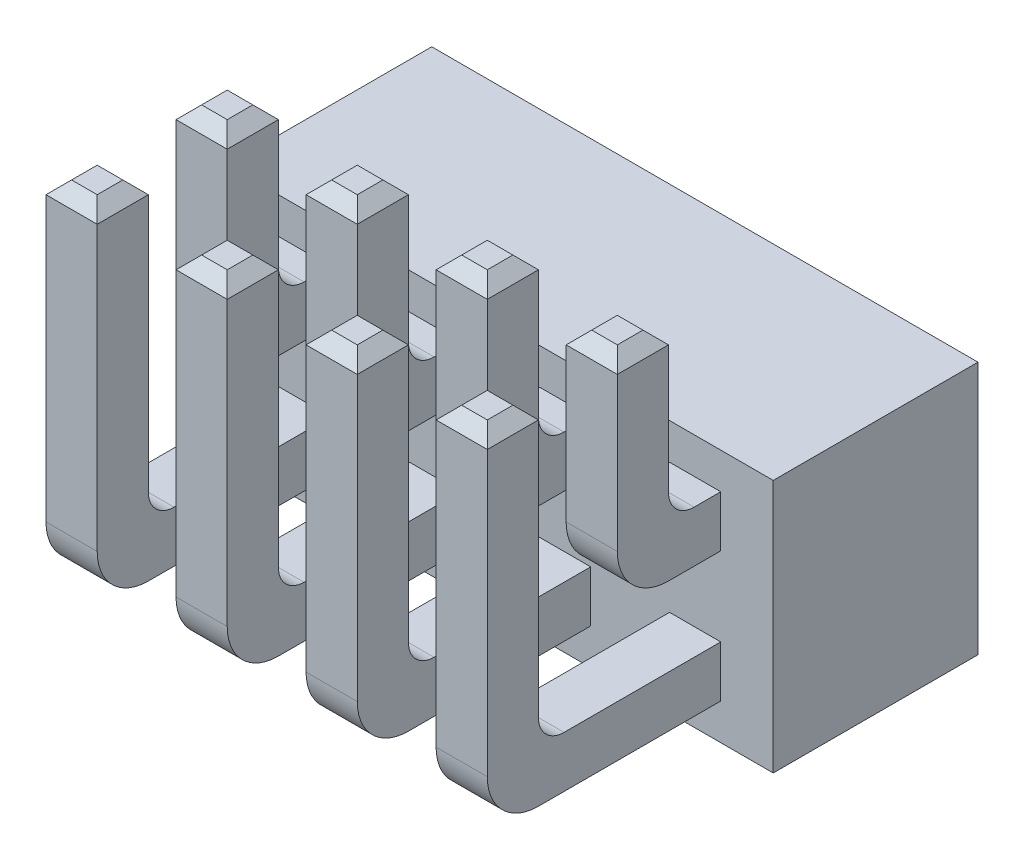
SolidWorks part; units mm, degrees
ref_plane "Front Plane" through (0, 0, 0) normal (0, 0, 1) x (1, 0, 0)
ref_plane "Top Plane" through (0, 0, 0) normal (0, 1, 0) x (1, 0, 0)
ref_plane "Right Plane" through (0, 0, 0) normal (1, 0, 0) x (0, 0, -1)
sketch "Sketch1" plane through (0, 0, 0) normal (0, 0, 1) x (1, 0, 0)
  line L1 (-5.335, 2.475) -> (5.335, 2.475)
  line L2 (-5.335, 2.475) -> (-5.335, -2.475)
  line L3 (-5.335, -2.475) -> (5.335, -2.475)
  line L4 (5.335, 2.475) -> (5.335, -2.475)
  line L5 (-5.335, 2.475) -> (5.335, -2.475) construction
  line L6 (-5.335, -2.475) -> (5.335, 2.475) construction
  point P0 (0, 0)
  point P10 (-8.3938, 4.4059)
  dimension "D1" = 10.67
  dimension "D2" = 4.95
extrude "Boss-Extrude1" add sketch "Sketch1" along normal blind 4
sketch "Sketch3" plane through (0, 0, 0) normal (0, 0, -1) x (-1, 0, 0)
  line L0 (-0.5788, 0.5788) -> (-1.9612, 0.5788)
  line L5 (-3.1188, 0.5788) -> (-4.5012, 0.5788)
  line L6 (-3.1188, 0.5788) -> (-3.1188, 1.9612)
  line L7 (-3.1188, 1.9612) -> (-4.5012, 1.9612)
  line L8 (-4.5012, 0.5788) -> (-4.5012, 1.9612)
  line L9 (-3.1188, 0.5788) -> (-4.5012, 1.9612) construction
  line L10 (-3.1188, 1.9612) -> (-4.5012, 0.5788) construction
  line L11 (-0.5788, 0.5788) -> (-0.5788, 1.9612)
  line L12 (-0.5788, 1.9612) -> (-1.9612, 1.9612)
  line L13 (-1.9612, 0.5788) -> (-1.9612, 1.9612)
  line L14 (-0.5788, 0.5788) -> (-1.9612, 1.9612) construction
  line L15 (-0.5788, 1.9612) -> (-1.9612, 0.5788) construction
  line L16 (1.9612, 0.5788) -> (0.5788, 0.5788)
  line L17 (1.9612, 0.5788) -> (1.9612, 1.9612)
  line L18 (1.9612, 1.9612) -> (0.5788, 1.9612)
  line L19 (0.5788, 0.5788) -> (0.5788, 1.9612)
  line L20 (1.9612, 0.5788) -> (0.5788, 1.9612) construction
  line L21 (1.9612, 1.9612) -> (0.5788, 0.5788) construction
  line L22 (4.5012, 0.5788) -> (3.1188, 0.5788)
  line L23 (4.5012, 0.5788) -> (4.5012, 1.9612)
  line L24 (4.5012, 1.9612) -> (3.1188, 1.9612)
  line L25 (3.1188, 0.5788) -> (3.1188, 1.9612)
  line L26 (4.5012, 0.5788) -> (3.1188, 1.9612) construction
  line L27 (4.5012, 1.9612) -> (3.1188, 0.5788) construction
  line L28 (-0.5788, -1.9612) -> (-1.9612, -1.9612)
  line L29 (-0.5788, -1.9612) -> (-0.5788, -0.5788)
  line L30 (-0.5788, -0.5788) -> (-1.9612, -0.5788)
  line L31 (-1.9612, -1.9612) -> (-1.9612, -0.5788)
  line L32 (-0.5788, -1.9612) -> (-1.9612, -0.5788) construction
  line L33 (-0.5788, -0.5788) -> (-1.9612, -1.9612) construction
  line L34 (1.9612, -1.9612) -> (0.5788, -1.9612)
  line L35 (1.9612, -1.9612) -> (1.9612, -0.5788)
  line L36 (1.9612, -0.5788) -> (0.5788, -0.5788)
  line L37 (0.5788, -1.9612) -> (0.5788, -0.5788)
  line L38 (1.9612, -1.9612) -> (0.5788, -0.5788) construction
  line L39 (1.9612, -0.5788) -> (0.5788, -1.9612) construction
  line L40 (4.5012, -1.9612) -> (3.1188, -1.9612)
  line L41 (4.5012, -1.9612) -> (4.5012, -0.5788)
  line L42 (4.5012, -0.5788) -> (3.1188, -0.5788)
  line L43 (3.1188, -1.9612) -> (3.1188, -0.5788)
  line L44 (4.5012, -1.9612) -> (3.1188, -0.5788) construction
  line L45 (4.5012, -0.5788) -> (3.1188, -1.9612) construction
  line L46 (-3.1188, -1.9612) -> (-4.5012, -1.9612)
  line L47 (-3.1188, -1.9612) -> (-3.1188, -0.5788)
  line L48 (-3.1188, -0.5788) -> (-4.5012, -0.5788)
  line L49 (-4.5012, -1.9612) -> (-4.5012, -0.5788)
  line L50 (-3.1188, -1.9612) -> (-4.5012, -0.5788) construction
  line L51 (-3.1188, -0.5788) -> (-4.5012, -1.9612) construction
  line L52 (-1.27, -1.27) -> (1.27, -1.27) construction
  line L53 (-3.81, 1.27) -> (-3.81, -1.27) construction
  point P0 (-3.81, 1.27)
  point P6 (-1.27, 1.27)
  point P12 (1.27, 1.27)
  point P17 (3.81, 1.27)
  point P22 (-1.27, -1.27)
  point P27 (1.27, -1.27)
  point P32 (3.81, -1.27)
  point P37 (-3.81, -1.27)
  point P42 (0, -1.27)
  point P46 (-3.81, 0)
  dimension "D3" = 2.54
  dimension "D4" = 2.54
  dimension "D1" = 4
  dimension "D2" = 2
extrude "Cut-Extrude1" cut sketch "Sketch3" against normal blind 3
sketch "Sketch4" plane through (0, 0, 0) normal (1, 0, 0) x (0, 0, -1)
  line L0 (-4, 0.77) -> (-5.02, 0.77)
  line L1 (-4, -2.475) -> (-4, 2.475) construction
  line L2 (-6.02, 1.77) -> (-6.02, 5.015)
  line L3 (-6.02, 5.015) -> (-5.02, 5.015)
  line L4 (-5.02, 5.015) -> (-5.02, 2.27)
  line L5 (-4.52, 1.77) -> (-4, 1.77)
  line L6 (-4, 1.77) -> (-4, 0.77)
  line L7 (-4, -1.77) -> (-7.56, -1.77)
  line L8 (-8.56, -0.77) -> (-8.56, 5.015)
  line L9 (-8.56, 5.015) -> (-7.56, 5.015)
  line L10 (-7.56, 5.015) -> (-7.56, -0.27)
  line L11 (-7.06, -0.77) -> (-4, -0.77)
  line L12 (-4, -0.77) -> (-4, -1.77)
  line L13 (-4, 2.475) -> (0, 2.475) construction
  line L14 (-4, -1.27) -> (-4, 1.27) construction
  arc A0 (-7.56, -0.27) -> (-7.06, -0.77) centre (-7.06, -0.27) ccw
  arc A1 (-5.02, 2.27) -> (-4.52, 1.77) centre (-4.52, 2.27) ccw
  arc A2 (-7.56, -1.77) -> (-8.56, -0.77) centre (-7.56, -0.77) cw
  arc A3 (-5.02, 0.77) -> (-6.02, 1.77) centre (-5.02, 1.77) cw
  point P10 (-5.52, 5.015)
  point P15 (-8.06, 5.015)
  point P18 (-4, -1.27)
  point P19 (-4, 1.27)
  point P22 (-4, 0)
  dimension "D6" = 0.5
  dimension "D7" = 1
  dimension "D1" = 2.54
  dimension "D2" = 2.54
  dimension "D3" = 1.52
  dimension "D4" = 1
  dimension "D5" = 2.54
extrude "Boss-Extrude2" add sketch "Sketch4" along normal blind 1 from offset 3.31
pattern_linear "LPattern1" count 4 spacing 2.54 along (-1, 0, 0) of "Boss-Extrude2"
chamfer "Chamfer1" distance 0.25 angle 45 32 edges at (-3.81, 5.015, 7.56) (-3.31, 5.015, 8.06) (-3.81, 5.015, 8.56) (-4.31, 5.015, 8.06) (-1.27, 5.015, 7.56) (-0.77, 5.015, 8.06) (-1.27, 5.015, 8.56) (-1.77, 5.015, 8.06) (1.27, 5.015, 7.56) (1.77, 5.015, 8.06) (1.27, 5.015, 8.56) (0.77, 5.015, 8.06) (3.81, 5.015, 7.56) (4.31, 5.015, 8.06) (3.81, 5.015, 8.56) (3.31, 5.015, 8.06) (3.81, 5.015, 5.02) (4.31, 5.015, 5.52) (3.81, 5.015, 6.02) (3.31, 5.015, 5.52) (1.27, 5.015, 5.02) (1.77, 5.015, 5.52) (1.27, 5.015, 6.02) (0.77, 5.015, 5.52) (-1.27, 5.015, 5.02) (-0.77, 5.015, 5.52) (-1.27, 5.015, 6.02) (-1.77, 5.015, 5.52) (-3.81, 5.015, 5.02) (-3.31, 5.015, 5.52) (-3.81, 5.015, 6.02) (-4.31, 5.015, 5.52)
